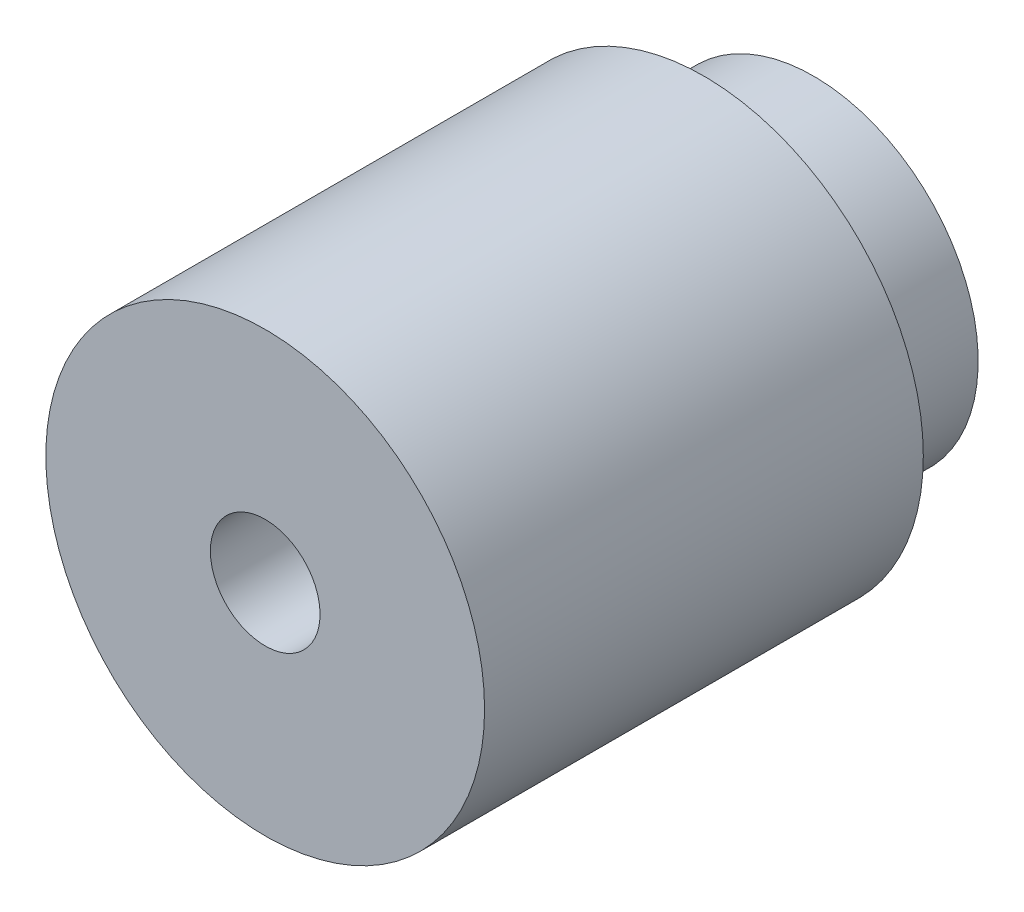
SolidWorks part; units mm, degrees
ref_plane "前视基准面" through (0, 0, 0) normal (0, 0, 1) x (1, 0, 0)
ref_plane "上视基准面" through (0, 0, 0) normal (0, 1, 0) x (1, 0, 0)
ref_plane "右视基准面" through (0, 0, 0) normal (1, 0, 0) x (0, 0, -1)
other "Configuration Table"
sketch "草图1" plane through (0, 0, 0) normal (0, 0, 1) x (1, 0, 0)
  circle A0 centre (0, 0) radius 20
extrude "凸台-拉伸1" add sketch "草图1" along normal blind 40
sketch "草图2" plane through (0, 0, 0) normal (0, 0, -1) x (-1, 0, 0)
  circle A0 centre (0, 0) radius 15
extrude "凸台-拉伸2" add sketch "草图2" along normal blind 10 separate body
sketch "草图3" plane through (0, 0, -10) normal (0, 0, -1) x (-1, 0, 0)
  circle A0 centre (0, 0) radius 5
extrude "切除-拉伸1" cut sketch "草图3" against normal blind 50
ref_plane "基准面1" through (0, 0, 20) normal (0, 0, 1) x (1, 0, 0)
sketch "草图6" plane through (0, 0, 20) normal (0, 0, 1) x (1, 0, 0)
  point P0 (0, 0)
sketch "草图7" plane through (0, 0, 20) normal (0, 0, 1) x (1, 0, 0)
  circle A0 centre (0, 0) radius 5 construction
  point P0 (5, 0)
  point P1 (-5, 0)
ref_axis "基准轴1" through (-25.9719, 0, 20) along (1, 0, 0)
sketch "草图8" plane through (0, 0, -10) normal (0, 0, -1) x (-1, 0, 0)
  line L4 (0, 0) -> (-15, 0)
  line L5 (25.9719, 0) -> (-24.9831, 0) construction
  circle A0 centre (0, 0) radius 15 construction
ref_point "点2"
ref_axis "基准轴2" through (0, 0, -10) along (0, 0, -1)
ref_axis "基准轴3" through (0, 0, -10) along (1, 0, 0)
